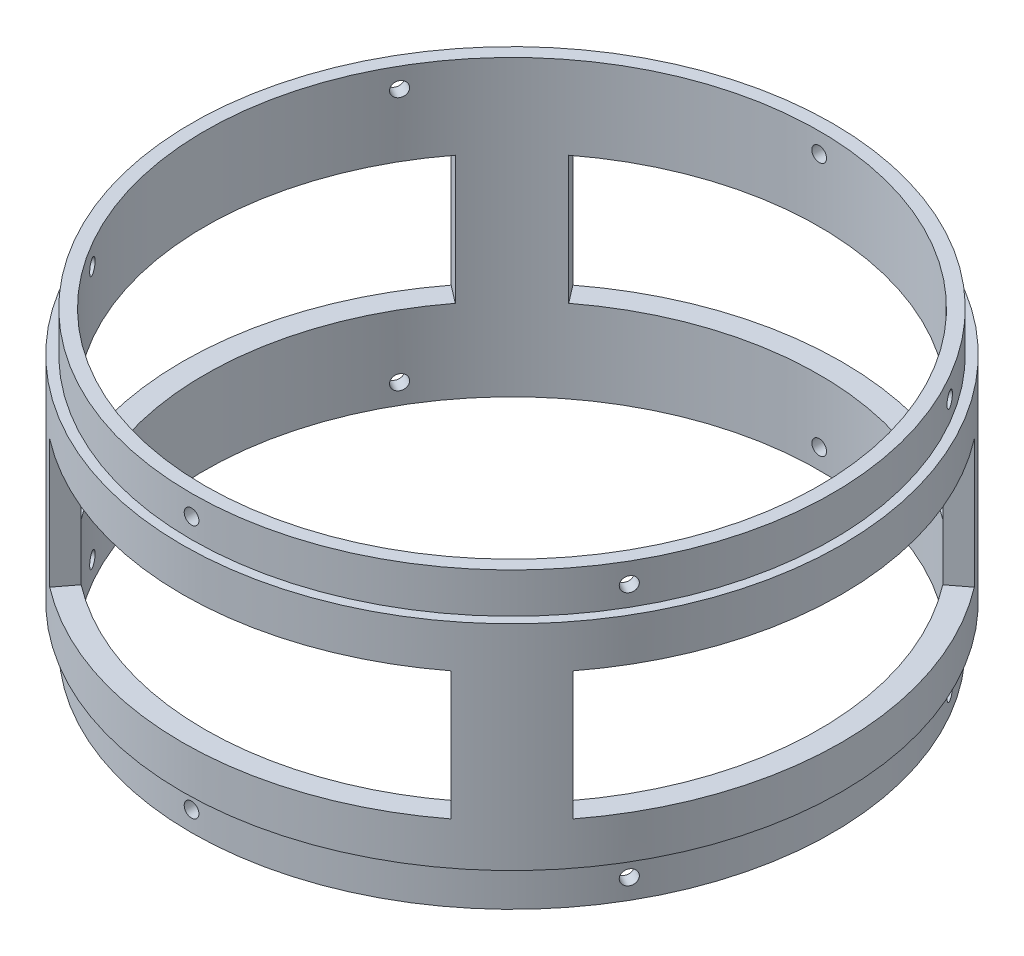
SolidWorks part; units mm, degrees
ref_plane "Front Plane" through (0, 0, 0) normal (0, 0, 1) x (1, 0, 0)
ref_plane "Top Plane" through (0, 0, 0) normal (0, 1, 0) x (1, 0, 0)
ref_plane "Right Plane" through (0, 0, 0) normal (1, 0, 0) x (0, 0, -1)
sketch "Sketch1" plane through (0, 0, 0) normal (0, 1, 0) x (1, 0, 0)
  line L0 (0, 0) -> (-47.7019, 62.1664)
  line L1 (0, 0) -> (47.7019, 62.1664)
  line L2 (0, 0) -> (0, 72.1431) construction
  circle A0 centre (0, 0) radius 78.359
  circle A1 centre (0, 0) radius 73.025
  circle A2 centre (0, 0) radius 76.1746
  dimension "D1" = 156.718
  dimension "D2" = 146.05
  dimension "D3" = 152.3492
  dimension "D4" = 75
extrude "Boss-Extrude1" add sketch "Sketch1" along normal blind 50.8 contours L2 A2 L1 A0 | L2 A1 L1 A2 | L2 A2 L1 A1 | L2 A0 L1 A2 | A2 L2 A1 L0 | A0 L2 A2 L0 | A2 L2 A0 L0 | A1 L2 A2 L0 region at (-33.2032, 0, 67.3294) region at (-44.6636, 0, -59.7594) region at (-34.6222, 0, 70.2068) region at (-46.2669, 0, -61.8908)
ref_plane "Plane1" through (0, 25.4, 0) normal (0, 1, 0) x (1, 0, 0)
extrude "Boss-Extrude2" add sketch "Sketch1<3>" along normal blind 9.525 from surface contours A2 L2 A1 L0 | L2 A2 L1 A1 | L2 A1 L1 A2 | A1 L2 A2 L0 region at (-33.2032, 0, 67.3294) region at (-44.6636, 0, -59.7594) starting at face at (0, 50.8, 73.025)
sketch "Sketch1<3>" plane through (0, 0, 0) normal (0, 1, 0) x (1, 0, 0) same geometry as "Sketch1"
extrude "Boss-Extrude3" add sketch "Sketch1<4>" against normal blind 9.525 contours A2 L2 A1 L0 | A1 L2 A2 L0 | L2 A1 L1 A2 | L2 A2 L1 A1 region at (-33.2032, 0, 67.3294) region at (-44.6636, 0, -59.7594)
sketch "Sketch1<4>" plane through (0, 0, 0) normal (0, 1, 0) x (1, 0, 0) same geometry as "Sketch1"
ref_plane "Plane2" through (0, 0, -76.1746) normal (0, 0, -1) x (-1, 0, 0)
ref_axis "Axis1" through (0, 0, 0) along (0, 1, 0)
sketch "Sketch3" plane through (0, 0, -76.1746) normal (0, 0, -1) x (-1, 0, 0)
  line L0 (76.1746, 0) -> (-76.1746, 0) construction
  line L1 (-76.1746, -9.525) -> (76.1746, -9.525) construction
  line L2 (76.1746, 50.8) -> (-76.1746, 50.8) construction
  line L3 (76.1746, 60.325) -> (-76.1746, 60.325) construction
  line L4 (76.1746, 0) -> (-76.1746, 0)
  line L5 (-76.1746, -9.525) -> (76.1746, -9.525)
  line L6 (76.1746, 50.8) -> (-76.1746, 50.8)
  line L7 (76.1746, 60.325) -> (-76.1746, 60.325)
  line L8 (0, 60.325) -> (0, 50.8)
  line L9 (0, 0) -> (0, -9.525)
  circle A0 centre (0, 55.5625) radius 1.75
  circle A1 centre (0, -4.7625) radius 1.75
  point P12 (0, 55.5625)
  point P13 (0, -4.7625)
  point P14 (-77.5445, 179.1871)
  dimension "D1" = 3.5
extrude "Cut-Extrude2" cut sketch "Sketch3" against normal up to next contours L8 A0 | L8 A0 | L9 A1 | L9 A1 region at (-0.7427, 55.5625, -76.1746) region at (0.7427, 55.5625, -76.1746) region at (-0.7427, -4.7625, -76.1746) region at (0.7427, -4.7625, -76.1746)
extrude "Cut-Extrude3" cut sketch "Sketch1<7>" against normal blind 15.24 and the other way blind 15.24 from surface contours L2 A1 L1 A2 | A1 L2 A2 L0 | A2 L2 A0 L0 | L2 A2 L1 A0 region at (-44.6636, 0, -59.7594) region at (-46.2669, 0, -61.8908) starting at plane "Plane1"
sketch "Sketch1<7>" plane through (0, 0, 0) normal (0, 1, 0) x (1, 0, 0) same geometry as "Sketch1"
pattern_circular "CirPattern2" count 4 over 360 about axis through (0, 0, 0) along (0, 1, 0) of "Cut-Extrude3"
pattern_circular "CirPattern3" count 6 over 360 about axis through (0, 0, 0) along (0, 1, 0) of "Cut-Extrude2"
equation "\"AB_Coupler_OD_Length\"= 2in"
equation "\"AB_Coupling_Section_Length\"= 0.375in"
equation "\"AB_Coupler_Length\"= \"AB_Coupler_OD_Length\" + \"AB_Coupling_Section_Length\" * 2"
equation "\"D1@Boss-Extrude2\"=\"AB_Coupling_Section_Length\""
equation "\"D1@Boss-Extrude3\"=\"AB_Coupling_Section_Length\""
equation "\"D1@Boss-Extrude1\" = \"AB_Coupler_OD_Length\""
equation "\"Cutout_Angle\"= 75"
equation "\"AB_Coupler_Num_Screws\"= 6"
equation "\"Num_Cutouts\"= 4"
equation "\"D4@Sketch1\"=\"Cutout_Angle\""
equation "\"D1@CirPattern2\"=\"Num_Cutouts\""
equation "\"D1@CirPattern3\"=\"AB_Coupler_Num_Screws\""
equation "\"AB_Coupler_OD\"= 6.17in"
equation "\"AB_Coupler_ID\"= 5.75in"
equation "\"AB_Coupler_Surface_Diameter\"= 5.998in"
equation "\"D3@Sketch1\"=\"AB_Coupler_Surface_Diameter\""
equation "\"D2@Sketch1\"=\"AB_Coupler_ID\""
equation "\"D1@Sketch1\"=\"AB_Coupler_OD\""
equation "\"AB_Coupling_Screw_Diameter\"= 3.5mm"
equation "\"Aft_Section_Length\"= 40in"
equation "\"Aft_Lower_Length\"= 20in"
equation "\"Aft_Upper_Length\"= \"Aft_Section_Length\" - \"Aft_Lower_Length\" - \"AB_Coupler_OD_Length\""
